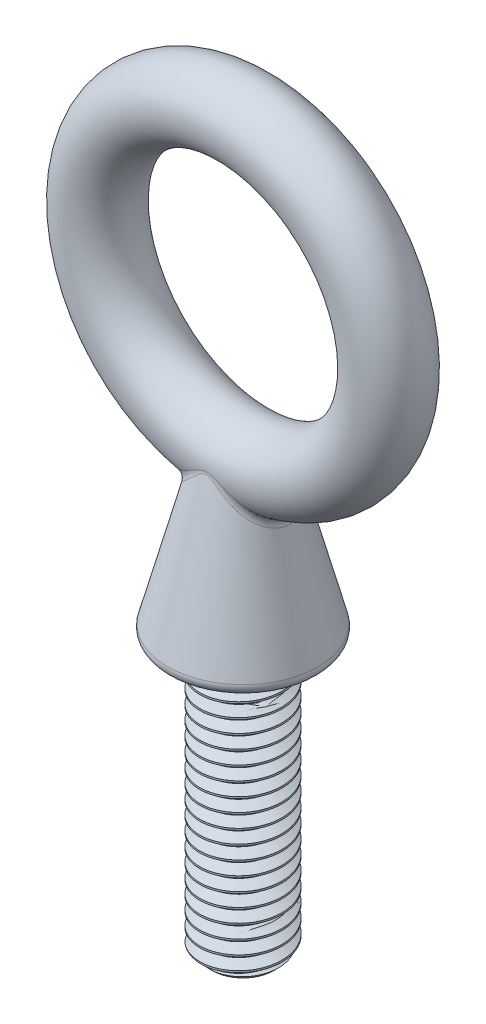
SolidWorks part; units mm, degrees
ref_plane "Front Plane" through (0, 0, 0) normal (0, 0, 1) x (1, 0, 0)
ref_plane "Top Plane" through (0, 0, 0) normal (0, 1, 0) x (1, 0, 0)
ref_plane "Right Plane" through (0, 0, 0) normal (1, 0, 0) x (0, 0, -1)
sketch "Sketch1" plane through (0, 0, 0) normal (0, 0, 1) x (1, 0, 0)
  line L0 (0, -21.0344) -> (0, -67.0719) construction
  line L1 (-4.7625, -67.0719) -> (4.7625, -67.0719) construction
  line L3 (0, -21.0344) -> (0, -12.7) construction
  line L4 (-8.7312, -35.3219) -> (8.7313, -35.3219) construction
  circle A0 centre (0, 0) radius 21.0344 construction
  circle A1 centre (0, 16.8672) radius 4.1672 construction
  circle A2 centre (0, 0) radius 12.7 construction
  point P7 (0, -21.0344)
  point P9 (0, -35.3219)
  point P10 (0, 21.0344)
  point P11 (0, 12.7)
  point P14 (0, -67.0719)
  point P19 (0, -16.8672)
  point P21 (0, -35.3219)
sketch "Sketch2" plane through (0, 0, 0) normal (0, 1, 0) x (1, 0, 0)
  circle A0 centre (0, 0) radius 4.7625
extrude "Boss-Extrude1" add sketch "Sketch2" against normal up to vertex (67.0719 mm away) from vertex at -35.3219 starting at point (0, -35.3219, 0)
sketch "Sketch3" plane through (0, -67.0719, 0) normal (0, -1, 0) x (1, 0, 0)
  circle A1 centre (0, 0) radius 4.7625
  circle A2 centre (0, 0) radius 4.7625
  point P0 (4.7625, 0)
  point P1 (0, -4.7625)
  dimension "D1" = 0
curve "Helix/Spiral1" pitch 1.5875 height 33.3375 turns 21 parameters "Pitch"=1.5875
sketch "Sketch4" plane through (0, 0, 0) normal (0, 0, 1) x (1, 0, 0)
  line L0 (4.9344, -66.9727) -> (4.9344, -68.5602) construction
  line L1 (4.9344, -68.5602) -> (3.5595, -67.7664) construction
  line L2 (3.5595, -67.7664) -> (4.9344, -66.9727) construction
  line L3 (3.7314, -67.6672) -> (3.7314, -67.8656) construction
  line L4 (4.7625, -67.0719) -> (4.7625, -68.4609) construction
  line L5 (3.5595, -67.7664) -> (3.7314, -67.7664) construction
  line L6 (4.7625, -67.7664) -> (4.9344, -67.7664) construction
  line L7 (4.8484, -67.0223) -> (3.7314, -67.6672)
  line L8 (3.7314, -67.6672) -> (3.7314, -67.8656)
  line L9 (3.7314, -67.8656) -> (4.8484, -68.5105)
  line L10 (4.8484, -68.5105) -> (4.8484, -67.0223)
  point P13 (4.8484, -67.7664)
  dimension "D1" = 1.5875
  dimension "D2" = 0.1984
sweep "Cut-Sweep1" cut profiles "Sketch4" path "Helix/Spiral1" align with end faces yes
sketch "Sketch5" plane through (0, -67.0719, 0) normal (0, -1, 0) x (1, 0, 0)
  circle A0 centre (0, 0) radius 3.5595
extrude "Cut-Extrude1" cut sketch "Sketch5" against normal through all draft 45 flip side to cut
sketch "Sketch6" plane through (0, 0, 0) normal (1, 0, 0) x (0, 0, -1)
  circle A0 centre (0, 16.8672) radius 4.1672
ref_axis "Axis1" through (0, 0, -7.6398) along (0, 0, 1)
revolve "Revolve1" add sketch "Sketch6" angle 360 about axis through (0, 0, -7.6398) along (0, 0, 1)
sketch "Sketch7" plane through (0, -35.3219, 0) normal (0, 1, 0) x (1, 0, 0)
  circle A1 centre (0, 0) radius 4.7625
  circle A2 centre (0, 0) radius 4.7625
  dimension "D1" = 0
extrude "Boss-Extrude2" [suppressed] add sketch "Sketch7" along normal up to vertex (9.525 mm away)
sketch "Sketch8" plane through (0, 0, 0) normal (0, 0, 1) x (1, 0, 0)
  line L0 (0, -35.3219) -> (0, -16.8672)
  line L1 (0, -16.8672) -> (-4.1672, -16.8672)
  line L2 (-7.6895, -35.3219) -> (-8.7312, -35.3219) construction
  line L3 (-8.7312, -35.3219) -> (-8.7312, -34.2801) construction
  line L5 (-8.7312, -35.3219) -> (8.7313, -35.3219) construction
  line L6 (-8.6967, -34.014) -> (-4.1672, -16.8672)
  line L9 (-7.6895, -35.3219) -> (0, -35.3219)
  arc A0 (-8.6967, -34.014) -> (-7.6895, -35.3219) centre (-7.6895, -34.2801) ccw
  circle A1 centre (0, -16.8672) radius 4.1672 construction
  dimension "D1" = 1.0418
revolve "Revolve2" add sketch "Sketch8" angle 360 about L0
fillet "Fillet1" radius 1.0418 1 edges at (4.338, -19.8199, 2.3783)
sketch "SketchX" plane through (0, 0, 0) normal (1, 0, 0) x (0, 0, -1)
  line L0 (4.7625, -67.0719) -> (4.7625, -41.275) construction
  dimension "D1" = 25.7969
equation "\"D3@Helix/Spiral1\" = \"Pitch@Helix/Spiral1\" + \"Thread Lg.@Sketch1\""
equation "\"D1@Sketch4\" = \"Pitch@Helix/Spiral1\""
equation "\"D2@Sketch4\" = \"D1@Sketch4\" / 8"
equation "\"D1@Sketch8\" = \"A@Sketch1\" / 8"
equation "\"D1@Fillet1\" = \"A@Sketch1\" / 8"
equation "\"D1@SketchX\" = 1 + \"Pitch@Helix/Spiral1\" /  4"
